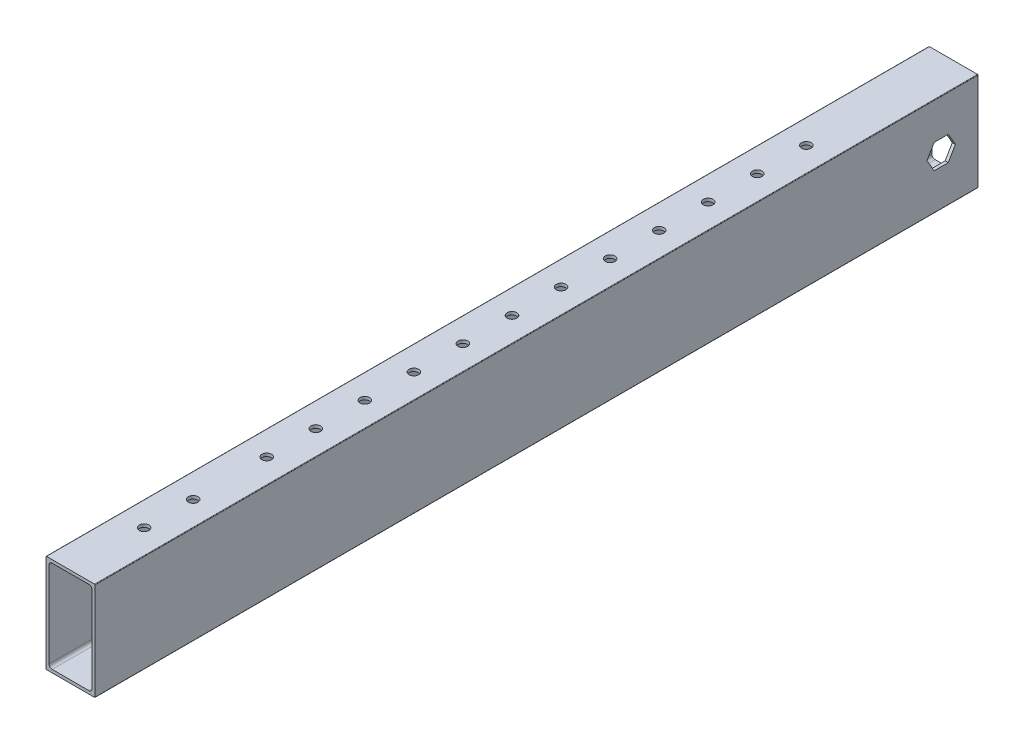
SolidWorks part; units mm, degrees
ref_plane "Front Plane" through (0, 0, 0) normal (0, 0, 1) x (1, 0, 0)
ref_plane "Top Plane" through (0, 0, 0) normal (0, 1, 0) x (1, 0, 0)
ref_plane "Right Plane" through (0, 0, 0) normal (1, 0, 0) x (0, 0, -1)
ref_plane "Plane1" through (0, 0, 0) normal (0, 0, -1) x (-1, 0, 0)
sketch "Sketch1" plane through (0, 0, 0) normal (0, 0, -1) x (-1, 0, 0)
  line L0 (-11.1125, -22.225) -> (-11.1125, 22.225)
  line L1 (-9.525, 23.8125) -> (9.525, 23.8125)
  line L2 (11.1125, 22.225) -> (11.1125, -22.225)
  line L3 (9.525, -23.8125) -> (-9.525, -23.8125)
  line L4 (-12.7, 25.146) -> (-12.7, -25.146)
  line L5 (-12.446, -25.4) -> (12.446, -25.4)
  line L6 (12.7, -25.146) -> (12.7, 25.146)
  line L7 (12.446, 25.4) -> (-12.446, 25.4)
  arc A0 (-11.1125, 22.225) -> (-9.525, 23.8125) centre (-9.525, 22.225) cw
  arc A1 (9.525, 23.8125) -> (11.1125, 22.225) centre (9.525, 22.225) cw
  arc A2 (11.1125, -22.225) -> (9.525, -23.8125) centre (9.525, -22.225) cw
  arc A3 (-9.525, -23.8125) -> (-11.1125, -22.225) centre (-9.525, -22.225) cw
  arc A4 (-12.7, -25.146) -> (-12.446, -25.4) centre (-12.446, -25.146) ccw
  arc A5 (12.446, -25.4) -> (12.7, -25.146) centre (12.446, -25.146) ccw
  arc A6 (12.7, 25.146) -> (12.446, 25.4) centre (12.446, 25.146) ccw
  arc A7 (-12.446, 25.4) -> (-12.7, 25.146) centre (-12.446, 25.146) ccw
extrude "Boss-Extrude1" add sketch "Sketch1" against normal blind 457.2
sketch "Sketch2" plane through (-12.7, 0, 0) normal (-1, 0, 0) x (0, 0, 1)
  line L0 (0, 0) -> (19.05, 0) construction
  line L2 (26.3823, 0) -> (22.7162, 6.35)
  line L3 (22.7162, 6.35) -> (15.3838, 6.35)
  line L4 (15.3838, 6.35) -> (11.7177, 0)
  line L5 (11.7177, 0) -> (15.3838, -6.35)
  line L6 (15.3838, -6.35) -> (22.7162, -6.35)
  line L7 (22.7162, -6.35) -> (26.3823, 0)
  circle A0 centre (19.05, 0) radius 6.35 construction
  dimension "D1" = 12.7
  dimension "D2" = 19.05
extrude "Cut-Extrude1" cut sketch "Sketch2" against normal blind 25.4
sketch "Sketch3" plane through (0, -25.4, 0) normal (0, -1, 0) x (1, 0, 0)
  line L0 (0, 0) -> (0, 457.2) construction
  line L1 (12.446, 457.2) -> (-12.446, 457.2) construction
  line L2 (12.446, 0) -> (-12.446, 0) construction
  line L3 (-12.7, 355.6) -> (12.7, 355.6) construction
  line L4 (-12.7, 457.2) -> (-12.7, 0) construction
  line L5 (12.7, 457.2) -> (12.7, 0) construction
  circle A0 centre (0, 76.2) radius 2.4892
  circle A1 centre (0, 101.6) radius 2.4892
  circle A2 centre (0, 127) radius 2.4892
  circle A3 centre (0, 152.4) radius 2.4892
  circle A4 centre (0, 177.8) radius 2.4892
  circle A5 centre (0, 203.2) radius 2.4892
  circle A6 centre (0, 228.6) radius 2.4892
  circle A7 centre (0, 254) radius 2.4892
  circle A8 centre (0, 279.4) radius 2.4892
  circle A9 centre (0, 304.8) radius 2.4892
  circle A10 centre (0, 330.2) radius 2.4892
  circle A11 centre (0, 393.7) radius 2.4892
  circle A12 centre (0, 419.1) radius 2.4892
  circle A13 centre (0, 355.6) radius 2.4892
  dimension "D1" = 76.2
  dimension "D2" = 4.9784
  dimension "D3" = 12
  dimension "D4" = 25.4
  dimension "D5" = 38.1
extrude "Cut-Extrude2" cut sketch "Sketch3" against normal through all both
